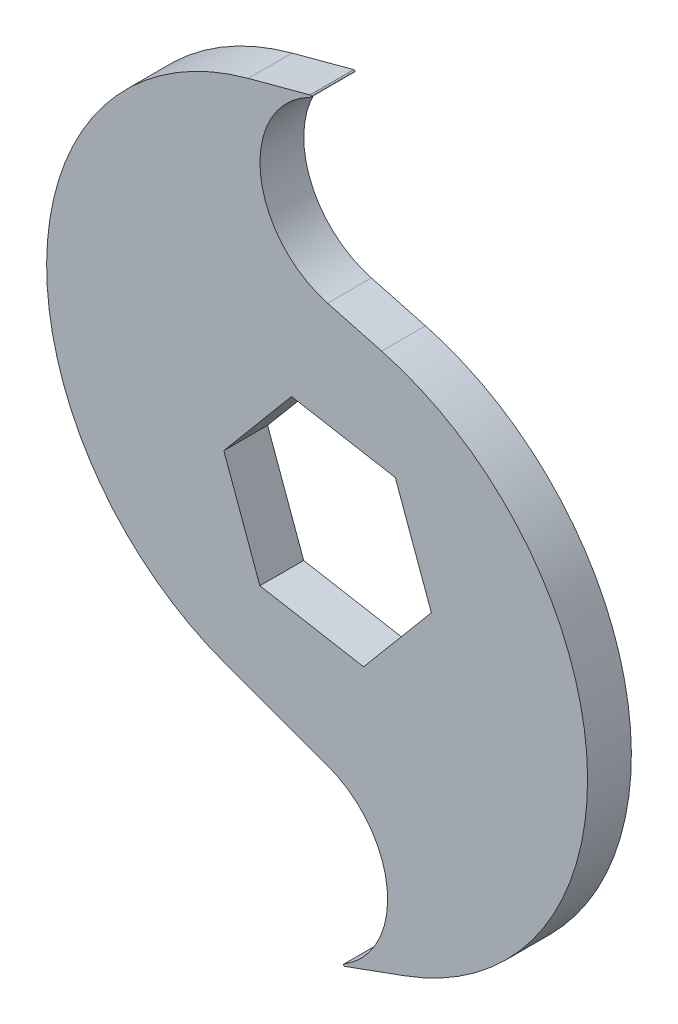
SolidWorks part; units mm, degrees
ref_plane "Front Plane" through (0, 0, 0) normal (0, 0, 1) x (1, 0, 0)
ref_plane "Top Plane" through (0, 0, 0) normal (0, 1, 0) x (1, 0, 0)
ref_plane "Right Plane" through (0, 0, 0) normal (1, 0, 0) x (0, 0, -1)
sketch "Sketch1" plane through (0, 0, 0) normal (0, 0, 1) x (1, 0, 0)
  line L0 (0, 52.07) -> (-11.0405, 49.1117)
  line L1 (0, 52.07) -> (0, 0) construction
  line L2 (0, -52.07) -> (10.7407, -48.1607)
  line L3 (0, 0) -> (0, -52.07) construction
  line L5 (-5.0156, 13.7803) -> (-14.4419, 2.5465)
  line L6 (-14.4419, 2.5465) -> (-9.4263, -11.2338)
  line L7 (-9.4263, -11.2338) -> (5.0156, -13.7803)
  line L8 (5.0156, -13.7803) -> (14.4419, -2.5465)
  line L9 (14.4419, -2.5465) -> (9.4263, 11.2338)
  line L10 (9.4263, 11.2338) -> (-5.0156, 13.7803)
  line L11 (0, 27.5355) -> (7.5237, 25.5195)
  line L12 (0, -28.2018) -> (-14.1906, -23.0368)
  circle A0 centre (0, 0) radius 52.07 construction
  arc A1 (0, 52.07) -> (0, 27.5355) centre (3.287, 39.8027) ccw
  arc A3 (0, -52.07) -> (0, -28.2018) centre (-4.3437, -40.1359) ccw
  arc A4 (10.7407, -48.1607) -> (7.5237, 25.5195) centre (-2.4834, -11.8278) ccw
  arc A5 (-11.0405, 49.1117) -> (-14.1906, -23.0368) centre (-1.2414, 12.5408) ccw
  circle A6 centre (0, 0) radius 12.7 construction
  dimension "D4" = 70
  dimension "D5" = 25.4
  dimension "D1" = 104.14
  dimension "D6" = 12.7
  dimension "D2" = 11.43
  dimension "D3" = 75
  dimension "D7" = 20
extrude "Boss-Extrude1" add sketch "Sketch1" along normal mid plane 6.096
fillet "Fillet1" radius 0.127 2 edges at (0, 52.07, 0) (0, -52.07, 0)
